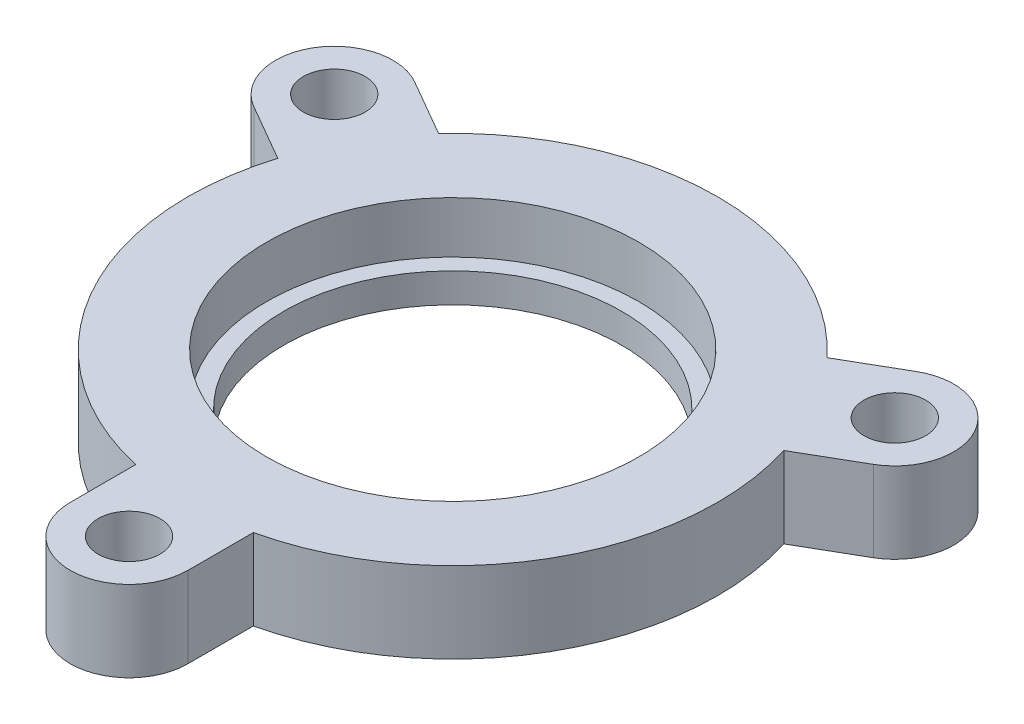
SolidWorks part; units mm, degrees
ref_plane "Front Plane" through (0, 0, 0) normal (0, 0, 1) x (1, 0, 0)
ref_plane "Top Plane" through (0, 0, 0) normal (0, 1, 0) x (1, 0, 0)
ref_plane "Right Plane" through (0, 0, 0) normal (1, 0, 0) x (0, 0, -1)
sketch "Sketch1" plane through (0, 0, 0) normal (0, 1, 0) x (1, 0, 0)
  line L0 (4, -22) -> (4, -17.5499)
  line L1 (-4, -22) -> (-4, -17.5499)
  line L2 (-21.0526, 7.5359) -> (-17.1987, 5.3109)
  line L3 (-17.0526, 14.4641) -> (-13.1987, 12.2391)
  line L4 (17.0526, 14.4641) -> (13.1987, 12.2391)
  line L5 (21.0526, 7.5359) -> (17.1987, 5.3109)
  circle A0 centre (0, 0) radius 18
  circle A1 centre (0, 0) radius 11.5
  circle A2 centre (0, -22) radius 4
  circle A3 centre (0, -22) radius 2.1
  circle A4 centre (0, 0) radius 12.65
  circle A5 centre (-19.0526, 11) radius 2.1
  circle A6 centre (-19.0526, 11) radius 4
  circle A7 centre (19.0526, 11) radius 2.1
  circle A8 centre (19.0526, 11) radius 4
  point P28 (0, 0)
  dimension "D2" = 36
  dimension "D3" = 23
  dimension "D4" = 4.2
  dimension "D5" = 8
  dimension "D6" = 25.3
  dimension "D1" = 22
  dimension "D7" = 3
extrude "Boss-Extrude1" add sketch "Sketch1" along normal blind 5.5 contours A2 L0 A0 | A2 A0 L1 | A2 A3 | A6 A5 | A6 A0 L3 | A6 L2 A0 | A8 A7 | A8 A0 L5 | A8 L4 A0 | A1 | A0 region at (3.0911, 0, 18.7412) region at (0, 0, 25.8869) region at (-3.0911, 0, 18.7412) region at (17.7759, 0, -6.6936) region at (-17.7759, 0, -6.6936) region at (18.0466, 0, -7.2456) region at (14.6848, 0, -12.0476) region at (-22.4187, 0, -12.9434) region at (-14.6848, 0, -12.0476) region at (0, 0, 0)
extrude "Cut-Extrude1" cut sketch "Sketch1<3>" against normal blind 3.5 from surface contours A4 starting at face at (0, 5.5, 0)
sketch "Sketch1<3>" plane through (0, 0, 0) normal (0, 1, 0) x (1, 0, 0) same geometry as "Sketch1"
